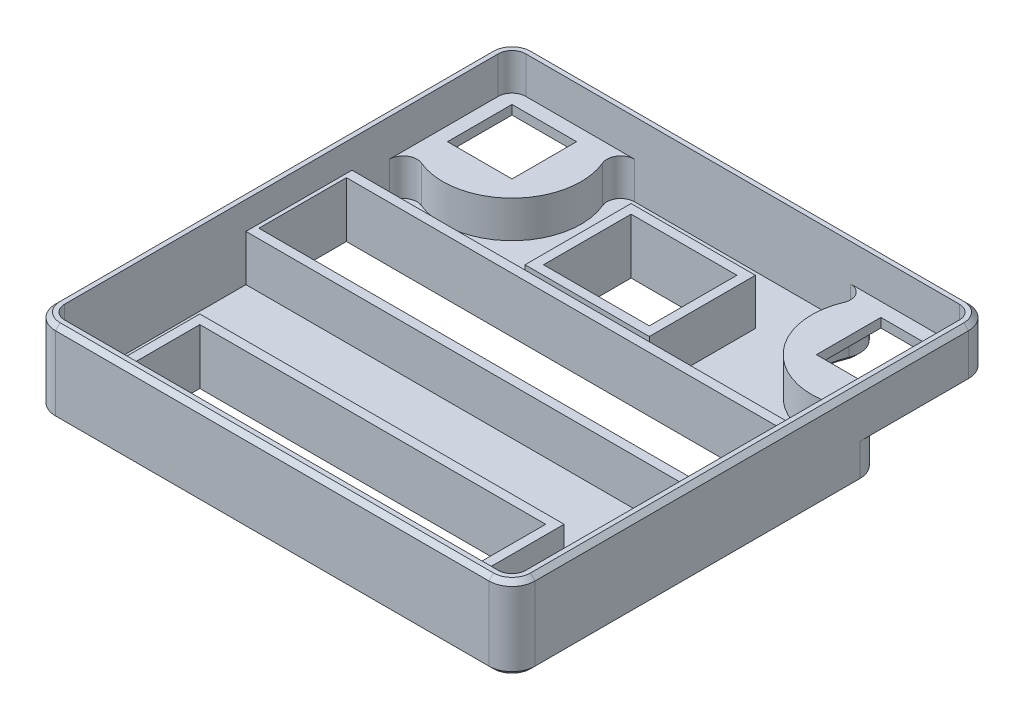
SolidWorks part; units mm, degrees
ref_plane "Front Plane" through (0, 0, 0) normal (0, 0, 1) x (1, 0, 0)
ref_plane "Top Plane" through (0, 0, 0) normal (0, 1, 0) x (1, 0, 0)
ref_plane "Right Plane" through (0, 0, 0) normal (1, 0, 0) x (0, 0, -1)
sketch "草图1" plane through (0, 0, 0) normal (0, 1, 0) x (1, 0, 0)
  line L1 (3, 0) -> (97, 0)
  line L2 (0, 3) -> (0, 97)
  line L3 (3, 100) -> (97, 100)
  line L4 (100, 3) -> (100, 97)
  line L7 (38.525, 87.3) -> (61.475, 87.3)
  line L8 (38.525, 87.3) -> (38.525, 68.3)
  line L9 (38.525, 68.3) -> (61.475, 68.3)
  line L10 (61.475, 87.3) -> (61.475, 68.3)
  line L11 (38.525, 87.3) -> (61.475, 68.3) construction
  line L12 (38.525, 68.3) -> (61.475, 87.3) construction
  line L13 (50, 0) -> (50, 9.9) construction
  line L14 (12.5, 19.8) -> (87.5, 19.8)
  line L15 (12.5, 19.8) -> (12.5, 0.8)
  line L16 (12.5, 0.8) -> (87.5, 0.8)
  line L17 (87.5, 19.8) -> (87.5, 0.8)
  line L18 (12.5, 19.8) -> (87.5, 0.8) construction
  line L19 (12.5, 0.8) -> (87.5, 19.8) construction
  line L20 (0.8, 63.3) -> (99.2, 63.3)
  line L21 (0.8, 63.3) -> (0.8, 44.3)
  line L22 (0.8, 44.3) -> (99.2, 44.3)
  line L23 (99.2, 63.3) -> (99.2, 44.3)
  line L24 (0.8, 63.3) -> (99.2, 44.3) construction
  line L25 (0.8, 44.3) -> (99.2, 63.3) construction
  arc A0 (0, 97) -> (3, 100) centre (3, 97) cw
  arc A1 (100, 97) -> (97, 100) centre (97, 97) ccw
  arc A2 (97, 0) -> (100, 3) centre (97, 3) ccw
  arc A3 (3, 0) -> (0, 3) centre (3, 3) cw
  point P6 (0, 100)
  point P12 (100, 0)
  point P15 (0, 0)
  point P16 (50, 77.8)
  point P17 (50, 0)
  point P22 (50, 10.3)
  point P29 (50, 53.8)
  point P30 (50, 68.3)
  point P31 (50, 63.3)
  dimension "D3" = 3
  dimension "D4" = 3
  dimension "D1" = 100
  dimension "D2" = 100
  dimension "D5" = 19
  dimension "D6" = 22.95
  dimension "D7" = 12.7
  dimension "D8" = 0.8
  dimension "D9" = 75
  dimension "D10" = 98.4
  dimension "D11" = 5
extrude "凸台-拉伸7" add sketch "草图1" along normal blind 2
sketch "草图4" plane through (0, 2, 0) normal (0, 1, 0) x (1, 0, 0)
  line L0 (3, 100) -> (97, 100) construction
  line L2 (0, 97) -> (0, 3) construction
  line L3 (100, 3) -> (100, 97) construction
  circle A0 centre (10, 90) radius 15
  circle A1 centre (90, 90) radius 15
  dimension "D1" = 10
  dimension "D3" = 30
  dimension "D4" = 10
  dimension "D6" = 30
  dimension "D2" = 10
  dimension "D5" = 10
extrude "切除-拉伸1" cut sketch "草图4" against normal blind 18
fillet "圆角1" radius 3 2 edges at (0, 1, -78.8197) (21.1803, 1, -100)
fillet "圆角2" radius 3 2 edges at (100, 1, -78.8197) (78.8197, 1, -100)
extrude "拉伸-薄壁3" add sketch "草图1<6>" along normal blind 12 thin contours L7 L10 L9 L8 thin type one direction wall 2
sketch "草图1<6>" plane through (0, 0, 0) normal (0, 1, 0) x (1, 0, 0) same geometry as "草图1"
extrude "拉伸-薄壁4" add sketch "草图1<7>" along normal blind 12 thin contours L22 L23 L20 L21 thin type one direction wall 2
sketch "草图1<7>" plane through (0, 0, 0) normal (0, 1, 0) x (1, 0, 0) same geometry as "草图1"
extrude "拉伸-薄壁5" add sketch "草图1<8>" along normal blind 12 thin contours L14 L17 L16 L15 thin type one direction wall 2
sketch "草图1<8>" plane through (0, 0, 0) normal (0, 1, 0) x (1, 0, 0) same geometry as "草图1"
sketch "草图10" plane through (0, 2, 0) normal (0, 1, 0) x (1, 0, 0)
  line L1 (26.5831, 100) -> (73.4169, 100)
  line L3 (3, 0) -> (97, 0) construction
  line L5 (0, 73.4169) -> (0, 3)
  line L6 (3, 0) -> (97, 0)
  line L7 (100, 3) -> (100, 73.4169)
  arc A0 (4.1667, 76.1807) -> (0, 73.4169) centre (3, 73.4169) ccw construction
  arc A1 (4.1667, 76.1807) -> (0, 73.4169) centre (3, 73.4169) ccw
  arc A2 (4.1667, 76.1807) -> (23.8193, 95.8333) centre (10, 90) ccw construction
  arc A3 (26.5831, 100) -> (23.8193, 95.8333) centre (26.5831, 97) ccw construction
  arc A4 (26.5831, 100) -> (23.8193, 95.8333) centre (26.5831, 97) ccw
  arc A5 (4.1667, 76.1807) -> (23.8193, 95.8333) centre (10, 90) ccw
  arc A6 (100, 73.4169) -> (95.8333, 76.1807) centre (97, 73.4169) ccw construction
  arc A7 (76.1807, 95.8333) -> (95.8333, 76.1807) centre (90, 90) ccw construction
  arc A8 (76.1807, 95.8333) -> (73.4169, 100) centre (73.4169, 97) ccw construction
  arc A9 (100, 73.4169) -> (95.8333, 76.1807) centre (97, 73.4169) ccw
  arc A10 (76.1807, 95.8333) -> (95.8333, 76.1807) centre (90, 90) ccw
  arc A11 (76.1807, 95.8333) -> (73.4169, 100) centre (73.4169, 97) ccw
  arc A12 (0, 3) -> (3, 0) centre (3, 3) ccw construction
  arc A13 (97, 0) -> (100, 3) centre (97, 3) ccw construction
  arc A14 (97, 0) -> (100, 3) centre (97, 3) ccw
  arc A15 (0, 3) -> (3, 0) centre (3, 3) ccw
extrude "拉伸-薄壁7" add sketch "草图10" along normal blind 18 from surface thin starting at face at (50, 0, -46.4213) thin type one direction wall 2
sketch "草图11" plane through (0, 18, 0) normal (0, 1, 0) x (1, 0, 0)
  line L1 (26.5831, 102) -> (73.4169, 102) construction
  line L8 (26.5831, 102) -> (73.4169, 102)
  line L11 (73.4169, 102) -> (102, 102)
  line L12 (26.5831, 102) -> (-2, 102)
  line L14 (-2, 73.4169) -> (26.5831, 73.4169)
  line L16 (102, 73.4169) -> (102, 3) construction
  line L19 (-2, 73.4169) -> (-2, 102)
  line L20 (26.5831, 102) -> (26.5831, 73.4169)
  line L21 (73.4169, 102) -> (73.4169, 73.4169)
  line L22 (73.4169, 73.4169) -> (102, 73.4169)
  line L23 (26.5831, 100) -> (73.4169, 100) construction
  line L24 (26.5831, 100) -> (73.4169, 100)
  line L25 (-2, 3) -> (-2, 73.4169) construction
  line L26 (-2, 3) -> (-2, 73.4169) construction
  line L27 (102, 73.4169) -> (102, 3) construction
  line L28 (102, 73.4169) -> (102, 102)
extrude "切除-拉伸8" cut sketch "草图11" against normal blind 10 contours L12 L19 L14 L20 | L11 L28 L22 L21
sketch "草图13" plane through (0, 8, 0) normal (0, 1, 0) x (1, 0, 0)
  line L6 (26.5831, 102) -> (26.5831, 100) construction
  line L10 (26.5831, 102) -> (26.5831, 100)
  line L11 (-2, 73.4169) -> (0, 73.4169)
  line L14 (-2, 3) -> (-2, 73.4169) construction
  line L15 (-2, 3) -> (-2, 73.4169) construction
  line L16 (-2, 73.4169) -> (-2, 97)
  line L17 (3, 102) -> (26.5831, 102)
  line L19 (3, 97) -> (17, 97)
  line L20 (3, 97) -> (3, 83)
  line L21 (3, 83) -> (17, 83)
  line L22 (17, 97) -> (17, 83)
  line L23 (3, 97) -> (17, 83) construction
  line L24 (3, 83) -> (17, 97) construction
  arc A3 (4.1667, 76.1807) -> (0, 73.4169) centre (3, 73.4169) ccw construction
  arc A4 (4.1667, 76.1807) -> (23.8193, 95.8333) centre (10, 90) ccw construction
  arc A5 (26.5831, 100) -> (23.8193, 95.8333) centre (26.5831, 97) ccw construction
  arc A13 (4.1667, 76.1807) -> (0, 73.4169) centre (3, 73.4169) ccw
  arc A15 (4.1667, 76.1807) -> (23.8193, 95.8333) centre (10, 90) ccw
  arc A16 (26.5831, 100) -> (23.8193, 95.8333) centre (26.5831, 97) ccw
  arc A17 (-2, 97) -> (3, 102) centre (3, 97) cw
  point P14 (10, 90)
  dimension "D1" = 5
  dimension "D2" = 12
  dimension "D3" = 12
  dimension "D4" = 14
  dimension "D5" = 14
extrude "凸台-拉伸8" add sketch "草图13" along normal blind 2
sketch "草图15" plane through (0, 8, 0) normal (0, 1, 0) x (1, 0, 0)
  line L0 (73.4169, 102) -> (97, 102)
  line L1 (102, 97) -> (102, 73.4169)
  line L8 (100, 73.4169) -> (102, 73.4169) construction
  line L13 (73.4169, 102) -> (73.4169, 100) construction
  line L14 (100, 73.4169) -> (102, 73.4169)
  line L15 (73.4169, 102) -> (73.4169, 100)
  line L16 (83, 97) -> (97, 97)
  line L17 (83, 97) -> (83, 83)
  line L18 (83, 83) -> (97, 83)
  line L19 (97, 97) -> (97, 83)
  line L20 (83, 97) -> (97, 83) construction
  line L21 (83, 83) -> (97, 97) construction
  arc A0 (100, 73.4169) -> (95.8333, 76.1807) centre (97, 73.4169) ccw construction
  arc A1 (100, 73.4169) -> (95.8333, 76.1807) centre (97, 73.4169) ccw
  arc A2 (102, 97) -> (97, 102) centre (97, 97) ccw
  arc A9 (76.1807, 95.8333) -> (95.8333, 76.1807) centre (90, 90) ccw construction
  arc A10 (76.1807, 95.8333) -> (73.4169, 100) centre (73.4169, 97) ccw construction
  arc A12 (76.1807, 95.8333) -> (95.8333, 76.1807) centre (90, 90) ccw
  arc A13 (76.1807, 95.8333) -> (73.4169, 100) centre (73.4169, 97) ccw
  point P13 (90, 90)
  dimension "D1" = 5
  dimension "D2" = 12
  dimension "D3" = 12
  dimension "D4" = 14
extrude "凸台-拉伸9" add sketch "草图15" along normal blind 2
sketch "草图18" plane through (0, 10, 0) normal (0, 1, 0) x (1, 0, 0)
  line L2 (0, 73.4169) -> (-2, 73.4169) construction
  line L3 (26.5831, 102) -> (26.5831, 100) construction
  line L6 (0, 73.4169) -> (-2, 73.4169)
  line L7 (26.5831, 102) -> (26.5831, 100)
  line L8 (-2, 97) -> (-2, 73.4169) construction
  line L9 (26.5831, 102) -> (3, 102) construction
  line L10 (-2, 97) -> (-2, 73.4169)
  line L11 (26.5831, 102) -> (3, 102)
  line L16 (0, 73.4169) -> (0, 97)
  line L17 (3, 100) -> (26.5831, 100)
  line L24 (73.4169, 102) -> (73.4169, 100) construction
  line L25 (73.4169, 102) -> (73.4169, 100)
  line L26 (100, 73.4169) -> (102, 73.4169) construction
  line L27 (100, 73.4169) -> (102, 73.4169)
  line L28 (73.4169, 102) -> (97, 102)
  line L29 (102, 97) -> (102, 73.4169)
  line L30 (73.4169, 100) -> (97, 100)
  line L31 (100, 97) -> (100, 73.4169)
  arc A0 (3, 102) -> (-2, 97) centre (3, 97) ccw construction
  arc A1 (3, 102) -> (-2, 97) centre (3, 97) ccw
  arc A6 (102, 97) -> (97, 102) centre (97, 97) ccw
  arc A7 (97, 100) -> (100, 97) centre (97, 97) cw
  arc A8 (0, 97) -> (3, 100) centre (3, 97) cw
  dimension "D1" = 5
  dimension "D2" = 3
  dimension "D3" = 3
extrude "凸台-拉伸12" add sketch "草图18" along normal blind 8
chamfer "倒角1" distance 1 angle 45 12 edges at (80.8076, 0, -80.8076) (99.7639, 0, -77.5835) (77.5835, 0, -99.7639) (50, 0, -102) (22.4165, 0, -99.7639) (19.1924, 0, -80.8076) (0.2361, 0, -77.5835) (-2, 0, -38.2084) (-0.5355, 0, 0.5355) (50, 0, 2) (102, 0, -38.2084) (100.5355, 0, 0.5355)
chamfer "倒角2" distance 1 angle 45 8 edges at (100.5355, 18, 0.5355) (50, 18, 2) (102, 18, -50) (-0.5355, 18, 0.5355) (50, 18, -102) (-2, 18, -50) (100.5355, 18, -100.5355) (-0.5355, 18, -100.5355)
